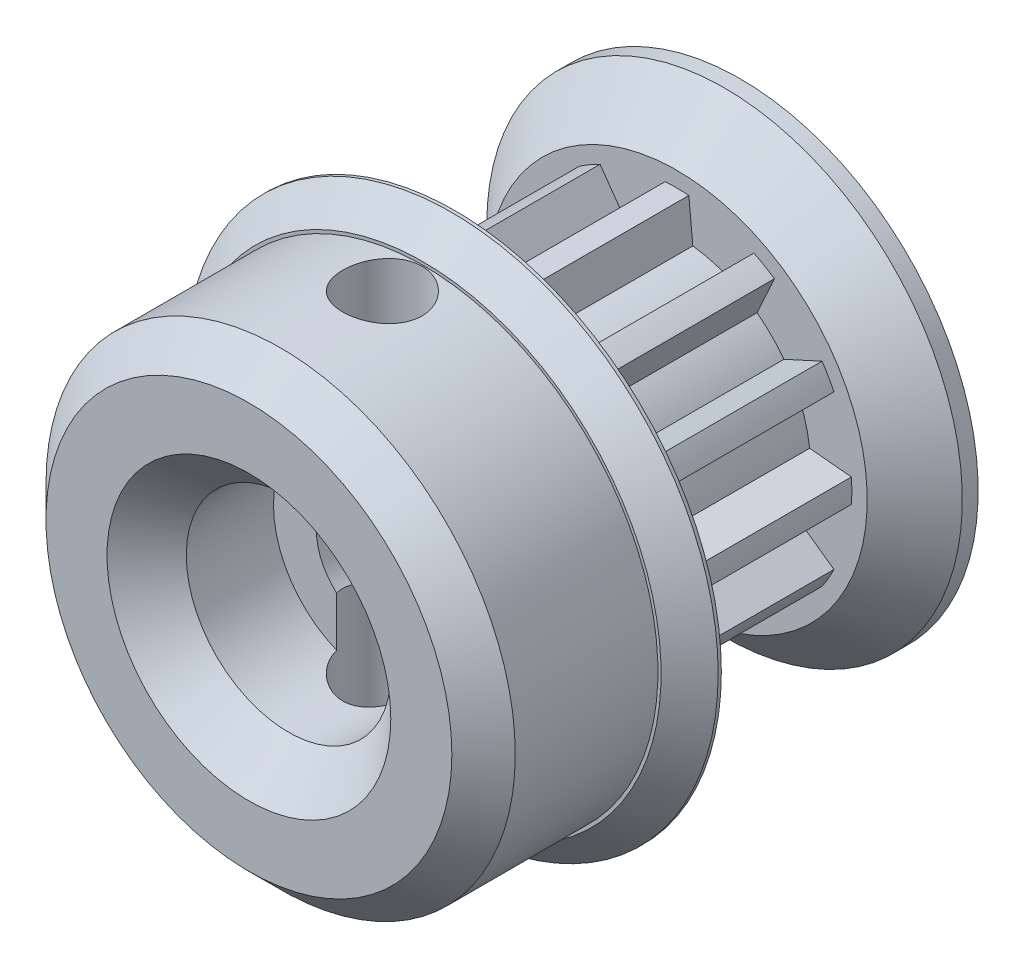
SolidWorks part; units mm, degrees
material "ABS"
ref_plane "Alzado" through (0, 0, 0) normal (0, 0, 1) x (1, 0, 0)
ref_plane "Planta" through (0, 0, 0) normal (0, 1, 0) x (1, 0, 0)
ref_plane "Vista lateral" through (0, 0, 0) normal (1, 0, 0) x (0, 0, -1)
sketch "Croquis1" plane through (0, 0, 0) normal (0, 0, 1) x (1, 0, 0)
  line L0 (0, 0) -> (0, 4.6049) construction
  line L1 (0.375, 5.5012) -> (0.5, 4.1842)
  line L2 (-0.375, 5.5012) -> (-0.5, 4.1842)
  line L3 (2.4259, 4.9517) -> (1.6591, 3.8737)
  line L4 (3.0754, 4.5767) -> (2.5251, 3.3737)
  line L5 (4.5767, 3.0754) -> (3.3737, 2.5251)
  line L6 (4.9517, 2.4259) -> (3.8737, 1.6591)
  line L7 (5.5012, 0.375) -> (4.1842, 0.5)
  line L8 (5.5012, -0.375) -> (4.1842, -0.5)
  line L9 (4.9517, -2.4259) -> (3.8737, -1.6591)
  line L10 (4.5767, -3.0754) -> (3.3737, -2.5251)
  line L11 (3.0754, -4.5767) -> (2.5251, -3.3737)
  line L12 (2.4259, -4.9517) -> (1.6591, -3.8737)
  line L13 (0.375, -5.5012) -> (0.5, -4.1842)
  line L14 (-0.375, -5.5012) -> (-0.5, -4.1842)
  line L15 (-2.4259, -4.9517) -> (-1.6591, -3.8737)
  line L16 (-3.0754, -4.5767) -> (-2.5251, -3.3737)
  line L17 (-4.5767, -3.0754) -> (-3.3737, -2.5251)
  line L18 (-4.9517, -2.4259) -> (-3.8737, -1.6591)
  line L19 (-5.5012, -0.375) -> (-4.1842, -0.5)
  line L20 (-5.5012, 0.375) -> (-4.1842, 0.5)
  line L21 (-4.9517, 2.4259) -> (-3.8737, 1.6591)
  line L22 (-4.5767, 3.0754) -> (-3.3737, 2.5251)
  line L23 (-3.0754, 4.5767) -> (-2.5251, 3.3737)
  line L24 (-2.4259, 4.9517) -> (-1.6591, 3.8737)
  circle A0 centre (0, 0) radius 1.875
  arc A1 (1.6591, 3.8737) -> (0.5, 4.1842) centre (0, 0) ccw
  arc A2 (3.0754, 4.5767) -> (2.4259, 4.9517) centre (0, 0) ccw
  arc A3 (4.9517, 2.4259) -> (4.5767, 3.0754) centre (0, 0) ccw
  arc A4 (5.5012, -0.375) -> (5.5012, 0.375) centre (0, 0) ccw
  arc A5 (4.5767, -3.0754) -> (4.9517, -2.4259) centre (0, 0) ccw
  arc A6 (2.4259, -4.9517) -> (3.0754, -4.5767) centre (0, 0) ccw
  arc A7 (-0.375, -5.5012) -> (0.375, -5.5012) centre (0, 0) ccw
  arc A8 (-3.0754, -4.5767) -> (-2.4259, -4.9517) centre (0, 0) ccw
  arc A9 (-4.9517, -2.4259) -> (-4.5767, -3.0754) centre (0, 0) ccw
  arc A10 (-5.5012, 0.375) -> (-5.5012, -0.375) centre (0, 0) ccw
  arc A11 (-4.5767, 3.0754) -> (-4.9517, 2.4259) centre (0, 0) ccw
  arc A12 (-2.4259, 4.9517) -> (-3.0754, 4.5767) centre (0, 0) ccw
  arc A13 (0.375, 5.5012) -> (-0.375, 5.5012) centre (0, 0) ccw
  arc A14 (3.3737, 2.5251) -> (2.5251, 3.3737) centre (0, 0) ccw
  arc A15 (4.1842, 0.5) -> (3.8737, 1.6591) centre (0, 0) ccw
  arc A16 (3.8737, -1.6591) -> (4.1842, -0.5) centre (0, 0) ccw
  arc A17 (2.5251, -3.3737) -> (3.3737, -2.5251) centre (0, 0) ccw
  arc A18 (0.5, -4.1842) -> (1.6591, -3.8737) centre (0, 0) ccw
  arc A19 (-1.6591, -3.8737) -> (-0.5, -4.1842) centre (0, 0) ccw
  arc A20 (-3.3737, -2.5251) -> (-2.5251, -3.3737) centre (0, 0) ccw
  arc A21 (-4.1842, -0.5) -> (-3.8737, -1.6591) centre (0, 0) ccw
  arc A22 (-3.8737, 1.6591) -> (-4.1842, 0.5) centre (0, 0) ccw
  arc A23 (-2.5251, 3.3737) -> (-3.3737, 2.5251) centre (0, 0) ccw
  arc A24 (-0.5, 4.1842) -> (-1.6591, 3.8737) centre (0, 0) ccw
  dimension "D1" = 1
  dimension "D2" = 3.75
  dimension "D4" = 1.3
  dimension "D3" = 0.75
  dimension "D6" = 1.2
  dimension "D5" = 12
extrude "Saliente-Extruir1" add sketch "Croquis1" along normal blind 7
sketch "Croquis2" plane through (0, 0, 7) normal (0, 0, 1) x (1, 0, 0)
  circle A0 centre (0, 0) radius 3.225
  circle A1 centre (0, 0) radius 7.4
  dimension "D1" = 14.8
  dimension "D2" = 6.45
extrude "Saliente-Extruir2" add sketch "Croquis2" along normal blind 6.5
chamfer "Chaflán1" distance 1 angle 45 1 edges at (7.4, 0, 13.5)
sketch "Croquis3" plane through (0, 0, 0) normal (0, 0, -1) x (-1, 0, 0)
  circle A0 centre (0, 0) radius 1.875
  circle A1 centre (0, 0) radius 7.5
  circle A2 centre (0, 0) radius 1.875 construction
  dimension "D1" = 15
extrude "Saliente-Extruir3" add sketch "Croquis3" along normal blind 2
chamfer "Chaflán2" distance 1.25 angle 45 1 edges at (3.225, 0, 13.5)
sketch "Croquis4" plane through (0, 0, 7) normal (0, 0, 1) x (1, 0, 0)
  circle A0 centre (0, 0) radius 1.875
  circle A1 centre (0, 0) radius 4.8926
  circle A2 centre (0, 0) radius 1.875 construction
extrude "Saliente-Extruir4" add sketch "Croquis4" along normal blind 2.5
chamfer "Chaflán3" distance 1 angle 45 12 edges at (4.0704, 1.0907, 7) (2.9798, 2.9798, 7) (1.0907, 4.0704, 7) (-1.0907, 4.0704, 7) (-2.9798, 2.9798, 7) (-4.0704, -1.0907, 7) (-4.0704, 1.0907, 7) (-2.9798, -2.9798, 7) (-1.0907, -4.0704, 7) (1.0907, -4.0704, 7) (2.9798, -2.9798, 7) (4.0704, -1.0907, 7)
chamfer "Chaflán4" distance 1.5 angle 45 1 edges at (-7.5, 0, 0)
sketch "Croquis6" plane through (0, 0, 7) normal (0, 0, -1) x (-1, 0, 0)
  circle A0 centre (0, 0) radius 8.4
  circle A1 centre (0, 0) radius 7.4 construction
  circle A2 centre (0, 0) radius 1.875
  circle A3 centre (0, 0) radius 1.875 construction
  dimension "D1" = 1
extrude "Saliente-Extruir5" add sketch "Croquis6" against normal blind 1
sketch "Croquis5" plane through (0, 0, 0) normal (0, 1, 0) x (1, 0, 0)
  line L0 (-9.2646, -3.6684) -> (10.0043, -3.6684) construction
  circle A0 centre (0, -9.2902) radius 1.25
  circle A1 centre (0, 1.9533) radius 1.25 construction
  dimension "D1" = 2.5
extrude "Cortar-Extruir1" cut sketch "Croquis5" against normal through all both and the other way through all
chamfer "Chaflán5" distance 0.9 angle 45 1 edges at (-8.4, 0, 8)
chamfer "Chaflán6" distance 1.2 angle 45 1 edges at (-1.875, 0, -2)
